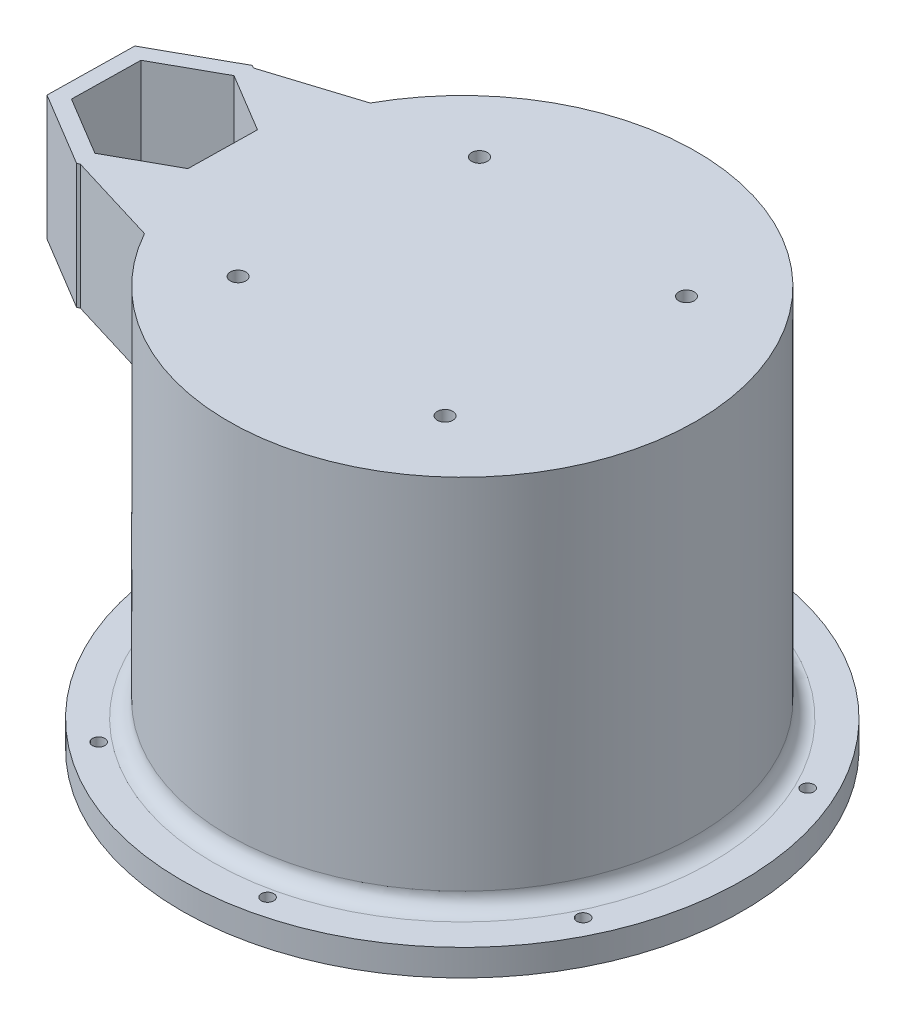
SolidWorks part; units mm, degrees
note: The reader was unsure of these and kept them because the rebuilt part matched: shared geometry of "Croquis4<3>", "Croquis8<5>".
ref_plane "Alzado" through (0, 0, 0) normal (0, 0, 1) x (1, 0, 0)
ref_plane "Planta" through (0, 0, 0) normal (0, 1, 0) x (1, 0, 0)
ref_plane "Vista lateral" through (0, 0, 0) normal (1, 0, 0) x (0, 0, -1)
sketch "Croquis4" plane through (0, 0, 0) normal (0, 1, 0) x (1, 0, 0)
  circle A0 centre (0, 0) radius 75
  circle A1 centre (0, 0) radius 90
  circle A2 centre (-83, 0) radius 2
  circle A3 centre (-51.7497, 64.892) radius 2
  circle A4 centre (18.4692, 80.919) radius 2
  circle A5 centre (74.7804, 36.0124) radius 2
  circle A6 centre (74.7804, -36.0124) radius 2
  circle A7 centre (18.4692, -80.919) radius 2
  circle A8 centre (-51.7497, -64.892) radius 2
  point P21 (0, 0)
  dimension "D1" = 150
  dimension "D3" = 4
  dimension "D4" = 7
  dimension "D2" = 15
  dimension "D5" = 7
extrude "Saliente-Extruir2" add sketch "Croquis4" along normal blind 125 contours A0
shell "Vaciado1" thickness 20
sketch "Croquis7" plane through (0, 125, 0) normal (0, 1, 0) x (1, 0, 0)
  circle A5 centre (38.717, 33.1963) radius 2.5
  circle A6 centre (33.1963, -38.717) radius 2.5
  circle A7 centre (-38.717, -33.1963) radius 2.5
  circle A8 centre (-33.1963, 38.717) radius 2.5
  dimension "D1" = 5
extrude "Cortar-Extruir3" cut sketch "Croquis7" against normal through all
extrude "Saliente-Extruir5" add sketch "Croquis4<3>" along normal blind 8.5 from offset 3.5 offset against normal yes
sketch "Croquis4<3>" plane through (0, 0, 0) normal (0, 1, 0) x (1, 0, 0) same geometry as "Croquis4"
sketch "Croquis8" plane through (0, 125, 0) normal (0, 1, 0) x (1, 0, 0)
  line L0 (-71.3003, 13.4508) -> (-95.0639, 27.7089)
  line L7 (-114.3428, 11.2877) -> (-114.7118, -10.6485)
  line L8 (-114.7118, -10.6485) -> (-95.899, -21.9362)
  line L9 (-95.899, -21.9362) -> (-76.7172, -11.2877)
  line L10 (-76.7172, -11.2877) -> (-76.3482, 10.6485)
  line L11 (-76.3482, 10.6485) -> (-95.161, 21.9362)
  line L12 (-95.161, 21.9362) -> (-114.3428, 11.2877)
  line L13 (-95.0639, 27.7089) -> (-119.2935, 14.2581)
  line L14 (-119.2935, 14.2581) -> (-119.7597, -13.4508)
  line L15 (-119.7597, -13.4508) -> (-95.9961, -27.7089)
  line L16 (-95.9961, -27.7089) -> (-71.7665, -14.2581)
  line L17 (-71.7665, -14.2581) -> (-71.3003, 13.4508)
  circle A0 centre (-95.53, 0) radius 19 construction
  circle A2 centre (-95.53, 0) radius 19
  dimension "D1" = 38
  dimension "D2" = 95.53
  dimension "D3" = 5
extrude "Saliente-Extruir7" add sketch "Croquis8" against normal blind 40 contours L15 L16 L0 L13 L14 L12 L11 L10 L9 L8 L7
fillet "Redondeo2" radius 5 1 edges at (0, 5, 75)
fillet "Redondeo4" radius 5 1 edges at (0, 105, 55)
extrude "Saliente-Extruir13" add sketch "Croquis8<5>" against normal blind 5 from surface at -40 separate body contours A2 L10 L11 | A2 L11 L12 | A2 L12 L7 | A2 L7 L8 | A2 L8 L9 | A2 L9 L10 starting at face at (-95.53, 85, 0)
sketch "Croquis8<5>" plane through (0, 125, 0) normal (0, 1, 0) x (1, 0, 0) same geometry as "Croquis8"
chamfer "Chaflán3" distance 30 angle 53 2 edges at (-73.5278, 105, -14.7872) (-73.4456, 105, 15.1903)
fillet "Redondeo6" radius 5 1 edges at (-75, 85, 0.0744)
